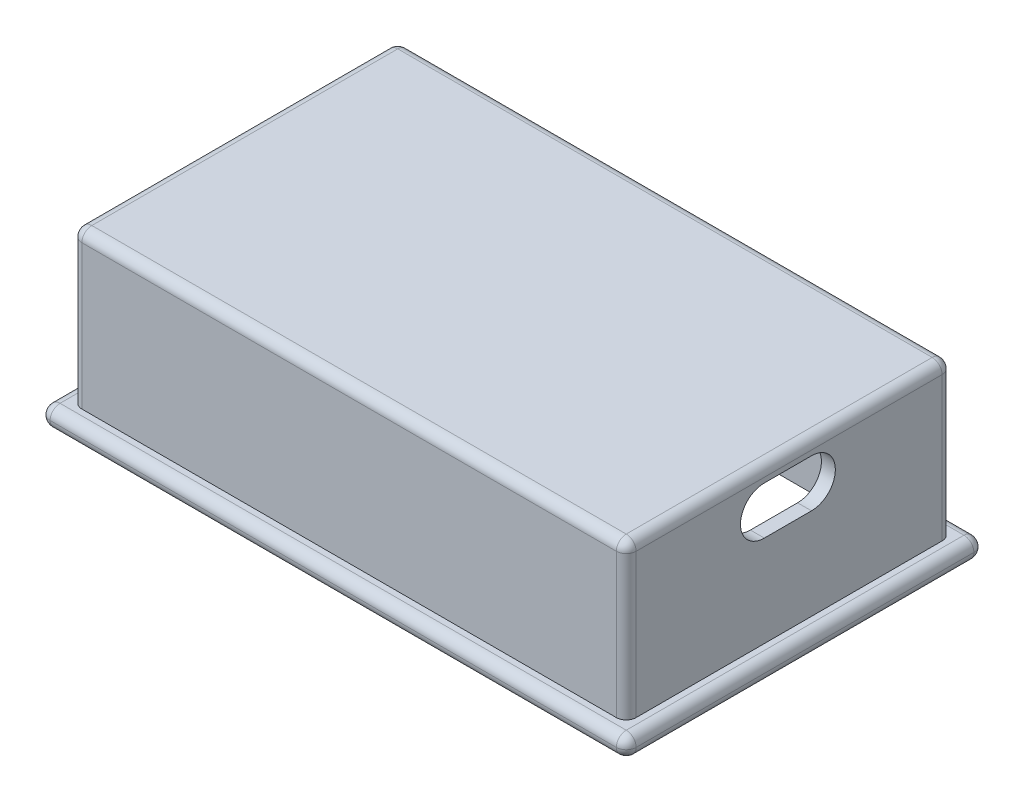
SolidWorks part; units mm, degrees
ref_plane "Front Plane" through (0, 0, 0) normal (0, 0, 1) x (1, 0, 0)
ref_plane "Top Plane" through (0, 0, 0) normal (0, 1, 0) x (1, 0, 0)
ref_plane "Right Plane" through (0, 0, 0) normal (1, 0, 0) x (0, 0, -1)
sketch "Sketch1" plane through (0, 0, 0) normal (0, 1, 0) x (1, 0, 0)
  line L1 (29.5, -18) -> (-29.5, -18)
  line L2 (29.5, -18) -> (29.5, 18)
  line L3 (29.5, 18) -> (-29.5, 18)
  line L4 (-29.5, -18) -> (-29.5, 18)
  line L5 (29.5, -18) -> (-29.5, 18) construction
  line L6 (29.5, 18) -> (-29.5, -18) construction
  point P0 (0, 0)
  dimension "D1" = 59
  dimension "D2" = 36
extrude "Boss-Extrude1" add sketch "Sketch1" along normal blind 17.5
sketch "Sketch2" plane through (0, 0, 0) normal (0, -1, 0) x (1, 0, 0)
  line L0 (-29.5, 18) -> (29.5, 18) construction
  line L1 (26.5, -15) -> (-26.5, -15)
  line L2 (26.5, -15) -> (26.5, 15)
  line L3 (26.5, 15) -> (-26.5, 15)
  line L4 (-26.5, -15) -> (-26.5, 15)
  line L5 (26.5, -15) -> (-26.5, 15) construction
  line L6 (26.5, 15) -> (-26.5, -15) construction
  line L7 (-29.5, -18) -> (-29.5, 18) construction
  line L8 (29.5, -18) -> (-29.5, -18) construction
  point P0 (0, 0)
  dimension "D1" = 3
  dimension "D2" = 3
  dimension "D3" = 3
extrude "Cut-Extrude1" cut sketch "Sketch2" against normal blind 15.9
sketch "Sketch3" plane through (0, 17.5, 0) normal (0, 1, 0) x (1, 0, 0)
  line L0 (29.5, 18) -> (-29.5, 18) construction
  line L1 (27.9, -16.4) -> (-27.9, -16.4)
  line L2 (27.9, -16.4) -> (27.9, 16.4)
  line L3 (27.9, 16.4) -> (-27.9, 16.4)
  line L4 (-27.9, -16.4) -> (-27.9, 16.4)
  line L5 (27.9, -16.4) -> (-27.9, 16.4) construction
  line L6 (27.9, 16.4) -> (-27.9, -16.4) construction
  line L7 (-29.5, 18) -> (-29.5, -18) construction
  point P0 (0, 0)
  dimension "D1" = 1.6
  dimension "D2" = 1.6
extrude "Cut-Extrude2" cut sketch "Sketch3" against normal blind 15.5 flip side to cut
sketch "Sketch4" plane through (27.9, 0, 0) normal (1, 0, 0) x (0, 0, -1)
  line L1 (2.25, 16) -> (-2.5, 16)
  line L5 (-16.4, 17.5) -> (16.4, 17.5) construction
  line L7 (2.25, 11.2) -> (-2.5, 11.2)
  arc A0 (2.25, 11.2) -> (2.25, 16) centre (2.25, 13.6) ccw
  arc A1 (-2.5, 16) -> (-2.5, 11.2) centre (-2.5, 13.6) ccw
  dimension "D7" = 4.8
  dimension "D1" = 2.4
  dimension "D2" = 1.5
  dimension "D5" = 2.4
extrude "Cut-Extrude3" cut sketch "Sketch4" against normal up to surface (1.4 mm away) up to face at (26.5, 7.95, 0)
fillet "Fillet1" radius 1 16 edges at (-29.5, 0, 0) (-29.5, 2, 0) (0, 0, -18) (0, 2, -18) (29.5, 0, 0) (29.5, 2, 0) (0, 0, 18) (0, 2, 18) (0, 17.5, -16.4) (27.9, 9.75, -16.4) (27.9, 17.5, 0) (27.9, 9.75, 16.4) (0, 17.5, 16.4) (-27.9, 17.5, 0) (-27.9, 9.75, -16.4) (-27.9, 9.75, 16.4)
